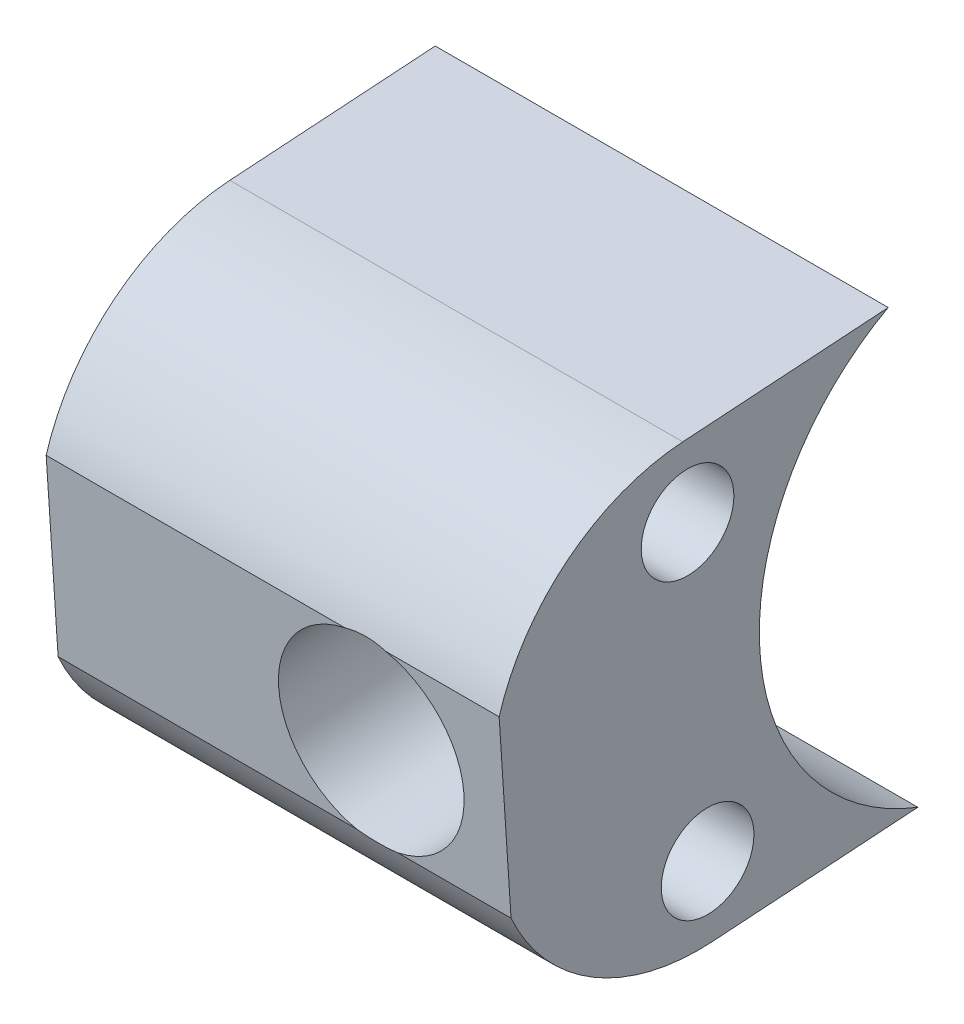
SolidWorks part; units mm, degrees
ref_plane "Front Plane" through (0, 0, 0) normal (0, 0, 1) x (1, 0, 0)
ref_plane "Top Plane" through (0, 0, 0) normal (0, 1, 0) x (1, 0, 0)
ref_plane "Right Plane" through (0, 0, 0) normal (1, 0, 0) x (0, 0, -1)
sketch "Sketch1" plane through (-10, 0, 0) normal (1, 0, 0) x (0, 0, -1)
  line L1 (-94.241, 40.7273) -> (-94.8205, 49.4874)
  line L2 (-74.4849, 35.5156) -> (-84.4631, 34.8556) construction
  line L3 (-85.9011, 56.5958) -> (-75.9229, 57.2559) construction
  line L4 (-74.4849, 35.5156) -> (-84.4631, 34.8556)
  line L5 (-85.9011, 56.5958) -> (-75.9229, 57.2559)
  arc A0 (-94.241, 40.7273) -> (-84.4631, 34.8556) centre (-85.1231, 44.8338) ccw construction
  arc A1 (-85.9011, 56.5958) -> (-94.8205, 49.4874) centre (-85.2411, 46.6176) ccw construction
  arc A2 (-94.241, 40.7273) -> (-84.4631, 34.8556) centre (-85.1231, 44.8338) ccw
  arc A3 (-85.9011, 56.5958) -> (-94.8205, 49.4874) centre (-85.2411, 46.6176) ccw
  arc A5 (-75.9229, 57.2559) -> (-74.4849, 35.5156) centre (-70.1826, 46.7179) ccw
extrude "Boss-Extrude1" add sketch "Sketch1" along normal blind 25
sketch "Sketch2" plane through (0, -6.2452, 91.134) normal (0, -0.066, 0.9978) x (1, 0, 0)
  line L0 (-14.5, 51.4648) -> (15, 51.4648) construction
  circle A0 centre (5.5, 51.4648) radius 4.5
  dimension "D2" = 9
  dimension "D1" = 20
extrude "Cut-Extrude1" cut sketch "Sketch2" against normal through all both and the other way through all
sketch "Sketch4" plane through (-10, 0, 0) normal (-1, 0, 0) x (0, 0, 1)
  circle A0 centre (85.6695, 53.094) radius 1
  circle A1 centre (84.6947, 38.3574) radius 1
extrude "Cut-Extrude3" cut sketch "Sketch4" against normal through all
sketch "Sketch5" plane through (15, 0, 0) normal (1, 0, 0) x (0, 0, -1)
  circle A0 centre (-84.6947, 38.3574) radius 2.25
  circle A1 centre (-85.6695, 53.094) radius 2.25
  dimension "D1" = 4.5
extrude "Cut-Extrude4" cut sketch "Sketch5" against normal blind 13
sketch "Sketch6" plane through (15, 0, 0) normal (1, 0, 0) x (0, 0, -1)
  circle A0 centre (-87.8456, 44.7805) radius 19.3261
extrude "Cut-Extrude5" cut sketch "Sketch6" against normal blind 3
